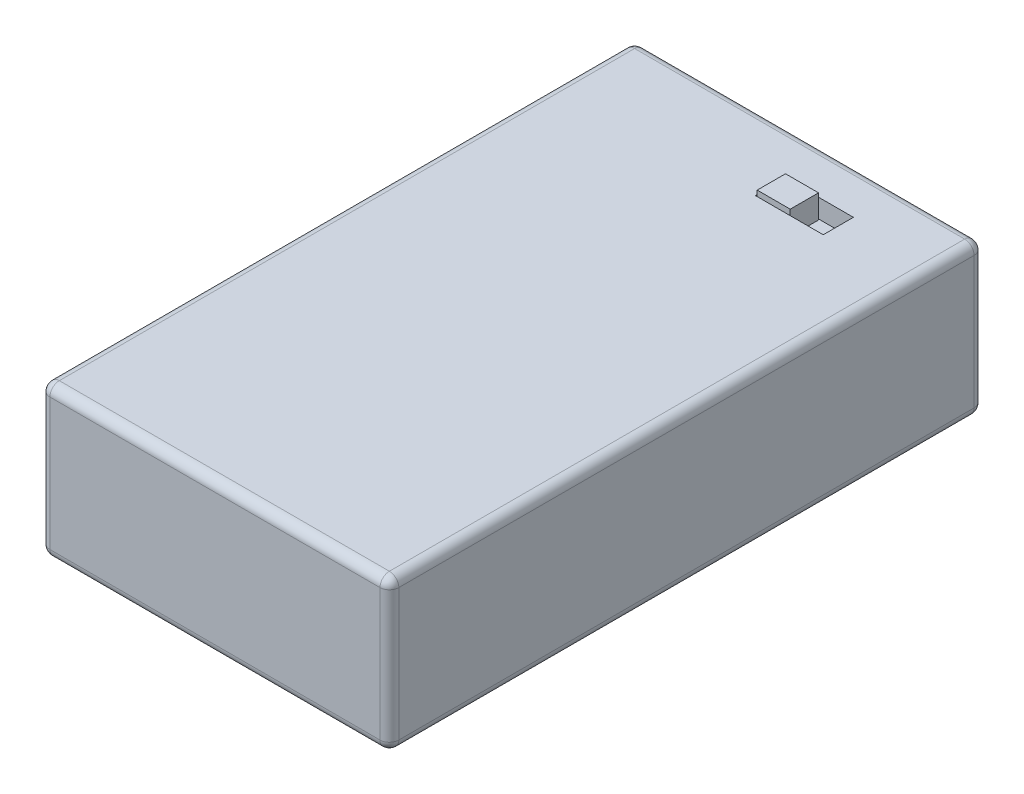
SolidWorks part; units mm, degrees
ref_plane "前视基准面" through (0, 0, 0) normal (0, 0, 1) x (1, 0, 0)
ref_plane "上视基准面" through (0, 0, 0) normal (0, 1, 0) x (1, 0, 0)
ref_plane "右视基准面" through (0, 0, 0) normal (1, 0, 0) x (0, 0, -1)
other "Configuration Table"
sketch "草图1" plane through (0, 0, 0) normal (0, 1, 0) x (1, 0, 0)
  line L1 (-18.5, -31.5) -> (18.5, -31.5)
  line L2 (-18.5, -31.5) -> (-18.5, 31.5)
  line L3 (-18.5, 31.5) -> (18.5, 31.5)
  line L4 (18.5, -31.5) -> (18.5, 31.5)
  line L5 (-18.5, -31.5) -> (18.5, 31.5) construction
  line L6 (-18.5, 31.5) -> (18.5, -31.5) construction
  line L19 (2.5, 26.5) -> (6, 26.5)
  line L20 (2.5, 26.5) -> (2.5, 23.5)
  line L29 (2.5, 23.5) -> (6, 23.5)
  line L30 (6, 26.5) -> (6, 23.5)
  line L31 (2.4, 26.6) -> (9.6, 26.6)
  line L32 (2.4, 26.6) -> (2.4, 23.4)
  line L33 (2.4, 23.4) -> (9.6, 23.4)
  line L34 (9.6, 26.6) -> (9.6, 23.4)
  point P0 (0, 0)
  point P14 (2.4, 25)
  point P15 (2.5, 25)
  dimension "D1" = 63
  dimension "D2" = 8
  dimension "D7" = 0.1
  dimension "D5" = 16
  dimension "D6" = 3.5
  dimension "D3" = 37
  dimension "D4" = 3
  dimension "D8" = 0.1
  dimension "D9" = 7.2
extrude "凸台-拉伸1" add sketch "草图1" along normal blind 16 contours L4 L3 L2 L1
fillet "圆角1" radius 1 12 edges at (18.5, 8, -31.5) (18.5, 8, 31.5) (-18.5, 8, -31.5) (-18.5, 8, 31.5) (0, 0, -31.5) (0, 16, -31.5) (0, 16, 31.5) (0, 0, 31.5) (18.5, 0, 0) (18.5, 16, 0) (-18.5, 0, 0) (-18.5, 16, 0)
extrude "切除-拉伸1" cut sketch "草图1<9>" against normal blind 2 from surface contours L31 L34 L33 L32 starting at face at (0, 16, 0)
sketch "草图1<9>" plane through (0, 0, 0) normal (0, 1, 0) x (1, 0, 0) same geometry as "草图1"
extrude "凸台-拉伸2" add sketch "草图1<10>" along normal blind 2.5 from surface contours L30 L29 L20 L19 starting at face at (6, 14, -25)
sketch "草图1<10>" plane through (0, 0, 0) normal (0, 1, 0) x (1, 0, 0) same geometry as "草图1"
